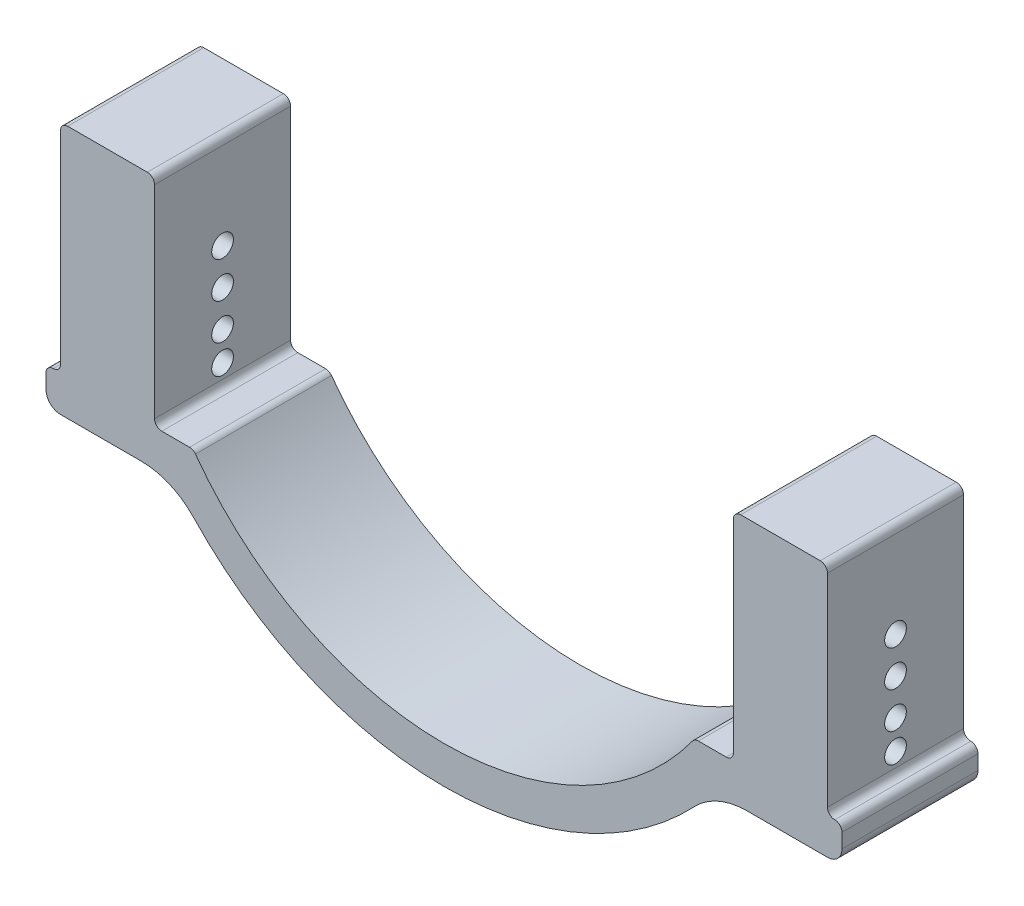
SolidWorks part; units mm, degrees
ref_plane "Front Plane" through (0, 0, 0) normal (0, 0, 1) x (1, 0, 0)
ref_plane "Top Plane" through (0, 0, 0) normal (0, 1, 0) x (1, 0, 0)
ref_plane "Right Plane" through (0, 0, 0) normal (1, 0, 0) x (0, 0, -1)
sketch "Sketch1" plane through (0, 0, 0) normal (0, 0, 1) x (1, 0, 0)
  line L0 (0, -20) -> (0, 17.3153) construction
  line L1 (53, 10) -> (40, 10)
  line L2 (53, 10) -> (53, -20)
  line L3 (53, -20) -> (55, -20)
  line L4 (40, 10) -> (40, -20)
  line L5 (40, -20) -> (34.641, -20)
  line L6 (-53, 10) -> (-40, 10)
  line L7 (-40, 10) -> (-40, -20)
  line L8 (-53, 10) -> (-53, -20)
  line L9 (-53, -20) -> (-55, -20)
  line L10 (-40, -20) -> (-34.641, -20)
  line L11 (55, -20) -> (55, -23)
  line L12 (53, -25) -> (41.8728, -25)
  line L13 (-55, -20) -> (-55, -23)
  line L14 (-53, -25) -> (-41.8728, -25)
  arc A0 (34.6092, -28.1268) -> (-34.6092, -28.1268) centre (0, 4.6221) cw
  circle A1 centre (0, 0) radius 40 construction
  arc A2 (34.641, -20) -> (-34.641, -20) centre (0, 4.6221) cw
  arc A4 (-41.8728, -25) -> (-34.6092, -28.1268) centre (-41.8728, -35) cw
  arc A5 (41.8728, -25) -> (34.6092, -28.1268) centre (41.8728, -35) ccw
  arc A6 (-55, -23) -> (-53, -25) centre (-53, -23) ccw
  arc A7 (55, -23) -> (53, -25) centre (53, -23) cw
  point P28 (-37.3205, -25)
  point P31 (37.3205, -25)
  point P34 (-55, -25)
  point P37 (55, -25)
  dimension "D3" = 42.5
  dimension "D4" = 10
  dimension "D5" = 2
  dimension "D1" = 17.6795
  dimension "D2" = 5
extrude "Boss-Extrude1" add sketch "Sketch1" along normal blind 18.8
sketch "Sketch2" plane through (-53, 0, 0) normal (-1, 0, 0) x (0, 0, 1)
  line L0 (9.4, 10) -> (9.4, -20) construction
  line L1 (18.8, 10) -> (0, 10) construction
  line L2 (18.8, -20) -> (0, -20) construction
  circle A0 centre (9.4, -13) radius 1.5
  circle A1 centre (9.4, -3) radius 1.5
  circle A2 centre (9.4, -8) radius 1.5
  circle A3 centre (9.4, -17) radius 1.5
  dimension "D1" = 3
  dimension "D2" = 3
  dimension "D3" = 3
  dimension "D4" = 3
extrude "Cut-Extrude1" cut sketch "Sketch2" against normal blind 168.8
fillet "Fillet1" radius 1 4 edges at (-40, -20, 9.4) (-34.641, -20, 9.4) (40, -20, 9.4) (34.641, -20, 9.4)
fillet "Fillet2" radius 1 8 edges at (-55, -20, 9.4) (-53, -20, 9.4) (-40, 10, 9.4) (-53, 10, 9.4) (55, -20, 9.4) (53, -20, 9.4) (53, 10, 9.4) (40, 10, 9.4)
